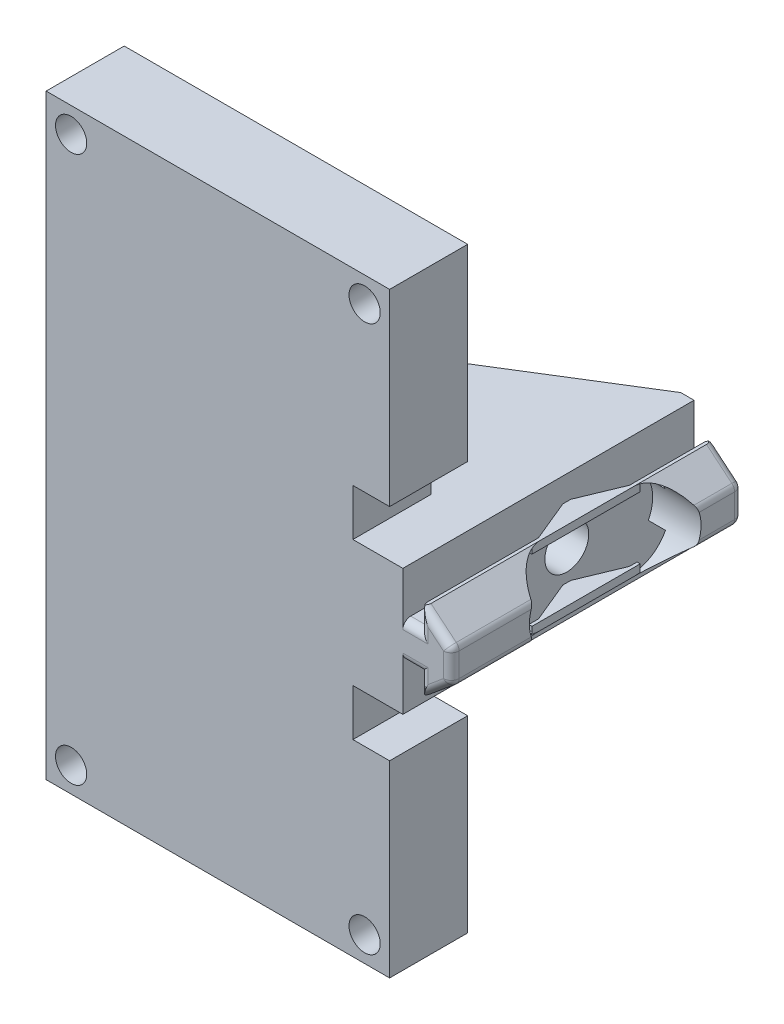
SolidWorks part; units mm, degrees
note: The reader was unsure of these and kept them because the rebuilt part matched: shared geometry of "Sketch21<3>".
ref_plane "Front Plane" through (0, 0, 0) normal (0, 0, 1) x (1, 0, 0)
ref_plane "Top Plane" through (0, 0, 0) normal (0, 1, 0) x (1, 0, 0)
ref_plane "Right Plane" through (0, 0, 0) normal (1, 0, 0) x (0, 0, -1)
ref_plane "Plane1" through (0, 0, 23.6855) normal (0, 0, 1) x (1, 0, 0)
sketch "Sketch1" plane through (0, 0, 23.6855) normal (0, 0, 1) x (1, 0, 0)
  line L0 (3.302, 6.35) -> (-4.064, 6.35)
  line L1 (-4.064, 6.35) -> (-4.064, -6.35)
  line L2 (-4.064, -6.35) -> (3.302, -6.35)
  line L3 (3.302, -6.35) -> (7.874, -2.54)
  line L4 (7.874, -2.54) -> (7.874, 2.54)
  line L5 (7.874, 2.54) -> (3.302, 6.35)
extrude "Boss-Extrude1" add sketch "Sketch1" against normal blind 47.371
sketch "Sketch2" plane through (0, 0, 23.6855) normal (0, 0, 1) x (1, 0, 0)
  line L0 (-4.064, 6.35) -> (-4.064, 2.921)
  line L1 (-4.064, 2.921) -> (2.794, 2.921)
  line L2 (2.794, 2.921) -> (2.794, 6.35)
  line L3 (2.794, 6.35) -> (-4.064, 6.35)
extrude "Cut-Extrude1" cut sketch "Sketch2" against normal through all
sketch "Sketch3" plane through (0, 2.921, 0) normal (0, 1, 0) x (-1, 0, 0)
  line L0 (4.064, -23.6855) -> (0, -23.6855)
  line L1 (0, -23.6855) -> (0, 23.6855)
  line L2 (0, 23.6855) -> (4.064, 23.6855)
  line L3 (4.064, 23.6855) -> (4.064, -23.6855)
extrude "Boss-Extrude2" add sketch "Sketch3" along normal blind 7.366
sketch "Sketch4" plane through (0, 0, 23.6855) normal (0, 0, 1) x (1, 0, 0)
  line L0 (-4.064, -6.35) -> (2.794, -6.35)
  line L1 (2.794, -6.35) -> (2.794, -2.921)
  line L2 (2.794, -2.921) -> (-4.064, -2.921)
  line L3 (-4.064, -2.921) -> (-4.064, -6.35)
extrude "Cut-Extrude2" cut sketch "Sketch4" against normal through all
sketch "Sketch5" plane through (0, -2.921, 0) normal (0, -1, 0) x (1, 0, 0)
  line L0 (0, -23.6855) -> (-4.064, -23.6855)
  line L1 (-4.064, -23.6855) -> (-4.064, 23.6855)
  line L2 (-4.064, 23.6855) -> (0, 23.6855)
  line L3 (0, 23.6855) -> (0, -23.6855)
extrude "Boss-Extrude3" add sketch "Sketch5" along normal blind 7.366
hole_wizard "#3 Clearance Hole1" [suppressed] positions "Sketch7" profile "Sketch6" hole size "#3" standard "ANSI Inch"
sketch "Sketch7" plane through (-4.064, 0, 0) normal (-1, 0, 0) x (0, 0, 1)
  point P0 (12.7, 0)
  point P1 (-12.7, 0)
sketch "Sketch6" plane through (-4.064, 0, 12.7) normal (0, 1, 0) x (0, 0, 1)
  line L0 (0, 0) -> (0, 11.938)
  line L1 (0, 11.938) -> (1.3843, 11.938)
  line L2 (1.3843, 11.938) -> (1.3843, 0)
  line L5 (1.3843, 0) -> (0, 0)
  line L11 (0, -6.35) -> (0, 107.95) construction
  dimension "Thru Hole Dia." = 2.7686
  dimension "Thru Hole Depth" = 11.938
sketch "Sketch12" [suppressed] plane through (7.874, 0, 0) normal (1, 0, 0) x (0, 0, -1)
  line L0 (-12.7, 1.3843) -> (-12.7, -1.3843) construction
  line L1 (12.7, 1.3843) -> (12.7, -1.3843) construction
  circle A0 centre (-12.7, 0) radius 1.3843 construction
  circle A1 centre (12.7, 0) radius 1.3843 construction
  point P5 (-12.7, 0)
  point P11 (12.7, 0)
hole_wizard "CBORE for #10 Button Head Cap Screw1" [suppressed] positions "Sketch13" profile "Sketch14" counterbore size "#10" standard "ANSI Inch"
sketch "Sketch13" [suppressed] plane through (7.874, 0, 0) normal (1, 0, 0) x (0, 0, -1)
  point P0 (-12.7, 0)
  point P3 (12.7, 0)
sketch "Sketch14" plane through (7.874, 0, 12.7) normal (0, 1, 0) x (0, 0, -1)
  line L0 (0, 0) -> (0, 11.938)
  line L1 (0, 11.938) -> (2.5527, 11.938)
  line L3 (2.5527, 11.938) -> (2.5527, 3.2004)
  line L4 (2.5527, 3.2004) -> (4.9606, 3.2004)
  line L5 (4.9606, 3.2004) -> (4.9606, 0)
  line L7 (4.9606, 0) -> (0, 0)
  line L11 (0, -6.35) -> (0, 107.95) construction
  dimension "Thru Hole Dia." = 5.1054
  dimension "Thru Hole Depth" = 11.938
  dimension "C'Bore Dia." = 9.9212
  dimension "C'Bore Depth" = 3.2004
fillet "Fillet1" radius 1.27 2 edges at (7.874, -2.54, 0) (7.874, 2.54, 0)
fillet "Fillet3" radius 1.27 9 edges at (5.3595, -4.6354, -23.6855) (7.7541, -2.4838, -23.6855) (5.3595, 4.6354, -23.6855) (7.7541, 2.4838, -23.6855) (1.397, -2.921, -23.6855) (1.397, 2.921, -23.6855) (2.794, 4.6355, -23.6855) (2.794, -4.6355, -23.6855) (7.874, 0, -23.6855)
fillet "Fillet5" radius 1.27 9 edges at (5.3595, -4.6354, 23.6855) (7.7541, -2.4838, 23.6855) (5.3595, 4.6354, 23.6855) (7.7541, 2.4838, 23.6855) (2.794, 4.6355, 23.6855) (1.397, 2.921, 23.6855) (1.397, -2.921, 23.6855) (2.794, -4.6355, 23.6855) (7.874, 0, 23.6855)
sketch "Sketch15" plane through (-4.064, 0, 0) normal (-1, 0, 0) x (0, 0, 1)
  line L1 (-23.6855, 10.287) -> (23.6855, 10.287)
  line L2 (-23.6855, 10.287) -> (-23.6855, -10.287)
  line L3 (-23.6855, -10.287) -> (23.6855, -10.287)
  line L4 (23.6855, 10.287) -> (23.6855, -10.287)
extrude "Cut-Extrude3" cut sketch "Sketch15" against normal blind 1.905
sketch "Sketch16" plane through (0, 0, 23.6855) normal (0, 0, 1) x (1, 0, 0)
  line L0 (-2.159, -10.287) -> (-2.159, 10.287) construction
  line L1 (-2.159, -48.514) -> (-58.039, -48.514)
  line L2 (-2.159, -48.514) -> (-2.159, 48.514)
  line L3 (-2.159, 48.514) -> (-58.039, 48.514)
  line L4 (-58.039, -48.514) -> (-58.039, 48.514)
  point P6 (-2.159, 0)
  dimension "D1" = 55.88
  dimension "D2" = 97.028
extrude "Boss-Extrude4" add sketch "Sketch16" against normal blind 12.7
sketch "Sketch17" plane through (0, 0, 23.6855) normal (0, 0, 1) x (1, 0, 0)
  line L0 (-58.039, -48.514) -> (-2.159, -48.514) construction
  line L1 (-53.975, 44.45) -> (-6.223, 44.45) construction
  line L2 (-53.975, 44.45) -> (-53.975, -44.45) construction
  line L3 (-53.975, -44.45) -> (-6.223, -44.45) construction
  line L4 (-6.223, 44.45) -> (-6.223, -44.45) construction
  line L6 (0, 10.287) -> (-8.128, 10.287)
  line L7 (0, 10.287) -> (0, 17.907)
  line L8 (0, 17.907) -> (-8.128, 17.907)
  line L9 (-8.128, 10.287) -> (-8.128, 17.907)
  line L10 (0, -10.287) -> (-8.128, -10.287)
  line L11 (0, -10.287) -> (0, -17.907)
  line L12 (0, -17.907) -> (-8.128, -17.907)
  line L13 (-8.128, -10.287) -> (-8.128, -17.907)
  circle A0 centre (-53.975, 44.45) radius 2.54
  circle A1 centre (-6.223, 44.45) radius 2.54
  circle A2 centre (-6.223, -44.45) radius 2.54
  circle A3 centre (-53.975, -44.45) radius 2.54
  point P4 (-6.223, 0)
  point P8 (-30.099, -48.514)
  point P9 (-30.099, -44.45)
  dimension "D3" = 5.08
  dimension "D1" = 47.752
  dimension "D2" = 88.9
  dimension "D4" = 7.62
  dimension "D5" = 8.128
extrude "Cut-Extrude4" cut sketch "Sketch17" against normal through all
sketch "Sketch18" plane through (0, 0, 0) normal (0, 1, 0) x (1, 0, 0)
  line L0 (-2.159, 23.6855) -> (-58.039, -10.9855)
  line L1 (-58.039, -10.9855) -> (-2.159, -10.9855)
  line L2 (-2.159, -10.9855) -> (-2.159, 23.6855)
extrude "Boss-Extrude5" add sketch "Sketch18" along normal blind 10.287 and the other way blind 10.287
sketch "Sketch19" plane through (0, 0, 0) normal (1, 0, 0) x (0, 0, -1)
  line L0 (-4.6355, 0) -> (10.6045, 0) construction
  line L1 (-4.6355, 6.35) -> (10.6045, 6.35)
  line L2 (-4.6355, -6.35) -> (10.6045, -6.35)
  line L3 (-23.6855, 55) -> (-23.6855, -55) construction
  arc A0 (-4.6355, 6.35) -> (-4.6355, -6.35) centre (-4.6355, 0) ccw
  arc A1 (10.6045, -6.35) -> (10.6045, 6.35) centre (10.6045, 0) ccw
  point P3 (2.9845, 0)
  point P8 (16.9545, 0)
  point P9 (-10.9855, 0)
  dimension "D1" = 27.94
  dimension "D2" = 12.7
  dimension "D3" = 12.7
extrude "Cut-Extrude5" cut sketch "Sketch19" along normal through all
sketch "Sketch21" plane through (0, -6.35, 0) normal (0, -1, 0) x (1, 0, 0)
  line L1 (2.794, 5.9888) -> (3.302, 5.9888)
  line L2 (2.794, 5.9888) -> (2.794, 4.4176)
  line L3 (2.794, -11.6156) -> (3.302, -11.6156)
  line L4 (3.302, 5.9888) -> (3.302, -11.6156)
  line L9 (-0.272, -2.9845) -> (2.794, 4.4176)
  line L10 (0, -23.6855) -> (0, 23.6855) construction
  line L11 (-0.272, -2.9845) -> (2.794, -10.3866)
  line L12 (2.794, -10.3866) -> (2.794, -11.6156)
  point P6 (2.794, -2.9845)
  dimension "D1" = 22.5
  dimension "D2" = 22.5
extrude "Boss-Extrude6" add sketch "Sketch21" against normal blind 1.27
extrude "Boss-Extrude7" add sketch "Sketch21<3>" along normal blind 1.27 from offset 12.7 offset against normal yes
sketch "Sketch21<3>" plane through (0, -6.35, 0) normal (0, -1, 0) x (1, 0, 0) same geometry as "Sketch21"
fillet "Fillet6" radius 0.254 2 edges at (3.048, 6.2041, 5.9888) (3.048, -6.2041, 5.9888)
ref_plane "Plane2" through (-50.8, 0, 0) normal (1, 0, 0) x (0, 0, -1)
hole_wizard "CBORE for 1/4 Button Head Cap Screw1" positions "Sketch26" profile "Sketch27" counterbore size "1/4" standard "ANSI Inch" end condition up to next
sketch "Sketch26" plane through (-50.8, 0, 0) normal (1, 0, 0) x (0, 0, -1)
  line L0 (-23.6855, 10.287) -> (-23.6855, 1.651) construction
  line L1 (10.6045, -6.35) -> (-4.6355, -6.35) construction
  point P0 (2.9845, 0)
  dimension "D1" = 26.67
  dimension "D2" = 6.35
sketch "Sketch27" plane through (-50.8, 0, -2.9845) normal (0, 1, 0) x (0, 0, 1)
  line L0 (0, 0) -> (0, 50.8)
  line L1 (0, 50.8) -> (3.5712, 50.8)
  line L3 (3.5712, 50.8) -> (3.5712, 38.1)
  line L4 (3.5712, 38.1) -> (5.9538, 38.1)
  line L5 (5.9538, 38.1) -> (5.9538, 0)
  line L7 (5.9538, 0) -> (0, 0)
  line L11 (0, -6.35) -> (0, 107.95) construction
  dimension "Thru Hole Dia." = 7.1425
  dimension "Thru Hole Depth" = 50.8
  dimension "C'Bore Dia." = 11.9075
  dimension "C'Bore Depth" = 38.1
